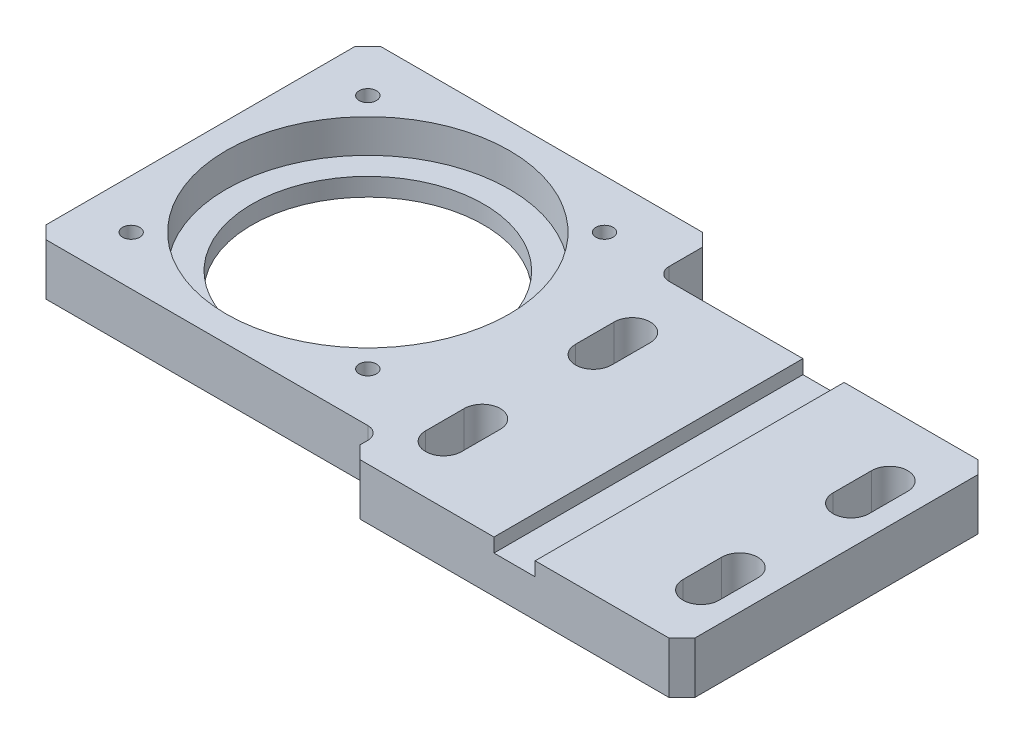
SolidWorks part; units mm, degrees
ref_plane "前视基准面" through (0, 0, 0) normal (0, 0, 1) x (1, 0, 0)
ref_plane "上视基准面" through (0, 0, 0) normal (0, 1, 0) x (1, 0, 0)
ref_plane "右视基准面" through (0, 0, 0) normal (1, 0, 0) x (0, 0, -1)
sketch "草图2" plane through (0, 0, 0) normal (0, 1, 0) x (1, 0, 0)
  line L0 (0, 0) -> (135, 0)
  line L1 (135, 0) -> (135, -23)
  line L2 (135, -23) -> (265, -23)
  line L3 (265, -23) -> (265, -143)
  line L4 (265, -143) -> (135, -143)
  line L5 (135, -143) -> (135, -130)
  line L6 (135, -130) -> (0, -130)
  line L7 (0, -130) -> (0, 0)
  point P9 (200, -143)
  dimension "D1" = 130
  dimension "D2" = 120
  dimension "D3" = 143
  dimension "D4" = 135
  dimension "D5" = 130
extrude "凸台-拉伸1" add sketch "草图2" along normal blind 20
sketch "草图3" plane through (0, 20, 0) normal (0, 1, 0) x (1, 0, 0)
  line L0 (0, 0) -> (0, -130) construction
  circle A0 centre (65, -65) radius 45
  point P5 (0, -65)
  dimension "D1" = 90
  dimension "D2" = 65
extrude "切除-拉伸1" cut sketch "草图3" against normal through all
sketch "草图4" plane through (0, 20, 0) normal (0, 1, 0) x (1, 0, 0)
  circle A0 centre (65, -65) radius 55
  dimension "D1" = 110
extrude "切除-拉伸2" cut sketch "草图4" against normal blind 13
sketch "草图5" plane through (0, 20, 0) normal (0, 1, 0) x (1, 0, 0)
  line L0 (192, -23) -> (192, -143)
  line L1 (265, -23) -> (135, -23) construction
  line L2 (135, -143) -> (265, -143) construction
  line L3 (208, -23) -> (208, -143)
  line L4 (200, -23) -> (200, -143) construction
  line L5 (265, -143) -> (265, -23) construction
  line L6 (192, -23) -> (208, -23)
  line L7 (208, -143) -> (192, -143)
  dimension "D1" = 65
  dimension "D2" = 16
extrude "切除-拉伸3" cut sketch "草图5" against normal blind 5.4
sketch "草图6" plane through (0, 20, 0) normal (0, 1, 0) x (1, 0, 0)
  line L0 (265, -83) -> (145.3453, -83) construction
  line L1 (265, -143) -> (265, -23) construction
  line L2 (200, -23) -> (200, -143) construction
  line L3 (208, -23) -> (192, -23) construction
  line L4 (192, -143) -> (208, -143) construction
  line L5 (150, -47.3125) -> (150, -62.3125) construction
  line L6 (157, -47.3125) -> (157, -62.3125)
  line L7 (143, -47.3125) -> (143, -62.3125)
  line L8 (150, -105.5582) -> (150, -120.5582) construction
  line L9 (157, -105.5582) -> (157, -120.5582)
  line L10 (143, -105.5582) -> (143, -120.5582)
  line L11 (250, -47.3125) -> (250, -62.3125) construction
  line L12 (257, -47.3125) -> (257, -62.3125)
  line L13 (243, -47.3125) -> (243, -62.3125)
  line L14 (250, -105.5582) -> (250, -120.5582) construction
  line L15 (257, -105.5582) -> (257, -120.5582)
  line L16 (243, -105.5582) -> (243, -120.5582)
  arc A0 (157, -47.3125) -> (143, -47.3125) centre (150, -47.3125) ccw
  arc A1 (143, -62.3125) -> (157, -62.3125) centre (150, -62.3125) ccw
  arc A2 (157, -105.5582) -> (143, -105.5582) centre (150, -105.5582) ccw
  arc A3 (143, -120.5582) -> (157, -120.5582) centre (150, -120.5582) ccw
  arc A4 (257, -47.3125) -> (243, -47.3125) centre (250, -47.3125) ccw
  arc A5 (243, -62.3125) -> (257, -62.3125) centre (250, -62.3125) ccw
  arc A6 (257, -105.5582) -> (243, -105.5582) centre (250, -105.5582) ccw
  arc A7 (243, -120.5582) -> (257, -120.5582) centre (250, -120.5582) ccw
  point P12 (150, -54.8125)
  point P17 (150, -113.0582)
  point P24 (250, -54.8125)
  point P31 (250, -113.0582)
  dimension "D2" = 29
  dimension "D1" = 14
  dimension "D3" = 100
extrude "切除-拉伸4" cut sketch "草图6" against normal through all
fillet "圆角1" radius 5 2 edges at (135, 10, 23) (135, 10, 130)
chamfer "倒角1" distance 5 6 edges at (265, 10, 23) (265, 10, 143) (135, 10, 143) (135, 10, 0) (0, 10, 130) (0, 10, 0)
sketch "草图7" plane through (0, 20, 0) normal (0, 1, 0) x (1, 0, 0)
  line L0 (65, -65) -> (65, 25.1133) construction
  line L1 (65, -65) -> (110.9619, -19.0381) construction
  circle A1 centre (65, -65) radius 65 construction
  circle A2 centre (110.9619, -19.0381) radius 3.35
  circle A3 centre (110.9619, -110.9619) radius 3.35
  circle A4 centre (19.0381, -110.9619) radius 3.35
  circle A5 centre (19.0381, -19.0381) radius 3.35
  point P15 (65, -65)
  dimension "D1" = 130
  dimension "D2" = 6.7
  dimension "D3" = 45
  dimension "D4" = 4
extrude "切除-拉伸5" cut sketch "草图7" against normal through all
